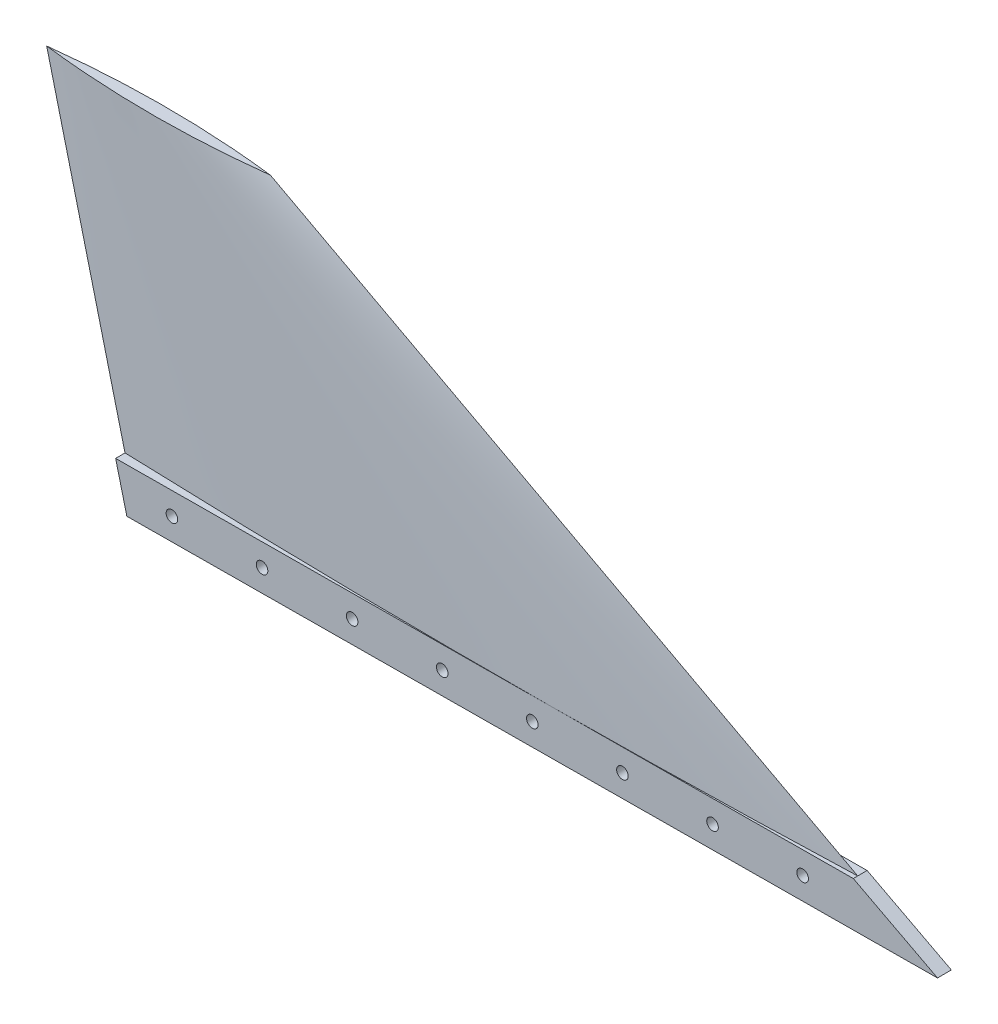
SolidWorks part; units mm, degrees
material "6061-T6 (SS)"
ref_plane "Front Plane" through (0, 0, 0) normal (0, 0, 1) x (1, 0, 0)
ref_plane "Top Plane" through (0, 0, 0) normal (0, 1, 0) x (1, 0, 0)
ref_plane "Right Plane" through (0, 0, 0) normal (1, 0, 0) x (0, 0, -1)
sketch "Sketch1" plane through (0, 0, 0) normal (0, 1, 0) x (1, 0, 0)
  line L0 (0, 0) -> (457.2, 0) construction
  line L1 (228.6, 3.81) -> (228.6, 0) construction
  arc A0 (0, 0) -> (457.2, 0) centre (228.6, -6856.095) cw
  arc A1 (0, 0) -> (457.2, 0) centre (228.6, 6856.095) ccw
  dimension "D1" = 457.2
  dimension "D2" = 3.81
ref_plane "Plane2" through (0, 203.2, 0) normal (0, 1, 0) x (1, 0, 0)
sketch "Sketch5" plane through (0, 203.2, 0) normal (0, 1, 0) x (1, 0, 0)
  line L0 (0, 0) -> (76.2, 0) construction
  line L1 (0, 0) -> (-50.8, 0) construction
  line L2 (12.7, 3.81) -> (12.7, 0) construction
  arc A0 (-50.8, 0) -> (76.2, 0) centre (12.7, -527.2617) cw
  arc A1 (-50.8, 0) -> (76.2, 0) centre (12.7, 527.2617) ccw
  dimension "D1" = 127
  dimension "D2" = 50.8
  dimension "D3" = 3.81
loft "Loft4" add profiles "Sketch5", "Sketch1" connector at (-50.8, 203.2, 0) connector at (0, 0, 0)
ref_axis "Axis3" through (228.6, 254.2969, 0) along (0, -1, 0)
ref_axis "Axis1" through (76.2, 203.2, 0) along (-1, 0, 0)
ref_axis "Axis2" through (457.2, 0, 0) along (-1, 0, 0)
ref_plane "Plane3" through (0.0106, 0, 1.556) normal (0.0068, 0, 1) x (0, -1, 0)
ref_plane "Plane8" through (-0.0175, 0, -2.569) normal (0.0068, 0, 1) x (0, -1, 0)
sketch "Sketch10" plane through (-0.0175, 0, -2.569) normal (0.0068, 0, 1) x (0, -1, 0)
  line L0 (0, 457.1894) -> (0, 0)
  line L1 (0, 0) -> (-25.4, -6.3499)
  line L2 (0, 0) -> (-203.2, -50.7988) construction
  line L3 (-25.4, -6.3499) -> (-25.4, 409.5655)
  line L4 (-203.2, 76.1982) -> (0, 457.1894) construction
  line L5 (-25.4, 409.5655) -> (0, 457.1894)
  dimension "D1" = 25.4
extrude "Boss-Extrude1" add sketch "Sketch10" along normal blind 7.8827
ref_plane "Plane5" through (0, 0, 0) normal (-1, 0, 0.0068) x (-0.0068, 0, -1)
sketch "Sketch12" plane through (0, 0, 0) normal (-1, 0, 0.0068) x (0.0068, 0, 1)
  line L2 (11.6637, 0) -> (11.6637, 25.4)
  line L4 (-8.919, 0) -> (-8.919, 25.4)
  line L5 (11.6637, 25.4) -> (5.3137, 25.4)
  line L6 (11.6637, 25.4) -> (11.6637, 0)
  line L7 (11.6637, 0) -> (5.3137, 0)
  line L8 (5.3137, 25.4) -> (5.3137, 0)
  line L9 (-8.919, 25.4) -> (-2.569, 25.4)
  line L10 (-8.919, 25.4) -> (-8.919, 0)
  line L11 (-8.919, 0) -> (-2.569, 0)
  line L12 (-2.569, 25.4) -> (-2.569, 0)
  line L14 (5.3137, 0) -> (-2.569, 0) construction
  dimension "D1" = 6.35
extrude "Cut-Extrude1" cut sketch "Sketch12" against normal through all both and the other way through all contours L5 L8 L7 L2 | L12 L9 L4 L11 region at (0.0578, 12.7, 8.4885) region at (-0.0391, 12.7, -5.7439)
ref_plane "Plane4" through (0.097, 0, 14.2557) normal (0.0068, 0, 1) x (0, -1, 0)
hole_wizard "1/4 Clearance Hole1" positions "Sketch8" profile "Sketch9" hole size "1/4" standard "ANSI Inch" end condition through all
sketch "Sketch8" plane through (0.097, 0, 14.2557) normal (0.0068, 0, 1) x (0, -1, 0)
  point P0 (-12.7, 25.4)
  dimension "D1" = 12.7
  dimension "D2" = 25.4
sketch "Sketch9" plane through (25.4964, 12.7, 14.0828) normal (0, 1, 0) x (1, 0, -0.0068)
  line L0 (0, 0) -> (0, 20.4303)
  line L1 (0, 20.4303) -> (3.2639, 20.4303)
  line L2 (3.2639, 20.4303) -> (3.2639, 0)
  line L5 (3.2639, 0) -> (0, 0)
  line L11 (0, -6.35) -> (0, 107.95) construction
  dimension "Thru Hole Dia." = 6.5278
  dimension "Thru Hole Depth" = 20.4303
pattern_linear "LPattern1" count 8 spacing 50.8 along (1, 0, 0) of "1/4 Clearance Hole1"
sketch "Sketch13" [suppressed] plane through (0, 0, 0) normal (0, -1, 0) x (1, 0, 0)
  line L0 (3.8884, 5.2873) -> (445.7919, 2.2793) construction
  line L1 (0.0362, 5.3135) -> (457.215, 2.2016) construction
  line L2 (-3.917, -2.5424) -> (450.1427, -5.6332) construction
  line L3 (-0.0175, -2.569) -> (457.1613, -5.6809) construction
  spline S0 degree 3 poles (-6.35, 0) (62.9148, 2.5382) (132.2636, 3.81) (214.4874, 3.81) (227.3622, 3.7662) (240.2365, 3.6785) knots 0.407173 0.407173 0.407173 0.407173 0.907173 0.907173 1 1 1 1 construction
  spline S1 degree 3 poles (227.5601, -3.7507) (218.911, -3.7902) (175.8551, -3.8887) (132.7993, -3.497) (98.403, -2.8715) knots 0.251931 0.251931 0.251931 0.251931 0.314292 0.562361 0.562361 0.562361 0.562361 construction
sketch "Sketch14" plane through (0.0362, 0, 5.3135) normal (0.0068, 0, 1) x (1, 0, -0.0068)
  line L0 (0, 0) -> (457.1894, 0) construction
  line L1 (-0.019, 0.0762) -> (457.1894, 0.0762)
  line L2 (-0.019, 0.0762) -> (-0.019, -25.3238)
  line L3 (-0.019, -25.3238) -> (457.1894, -25.3238)
  line L4 (457.1894, 0.0762) -> (457.1894, -25.3238)
  line L5 (-6.3499, 25.4) -> (0, 0) construction
  point P8 (0, 0)
  dimension "D1" = 0.0762
  dimension "D2" = 25.4
extrude "Cut-Extrude2" cut sketch "Sketch14" against normal through all
